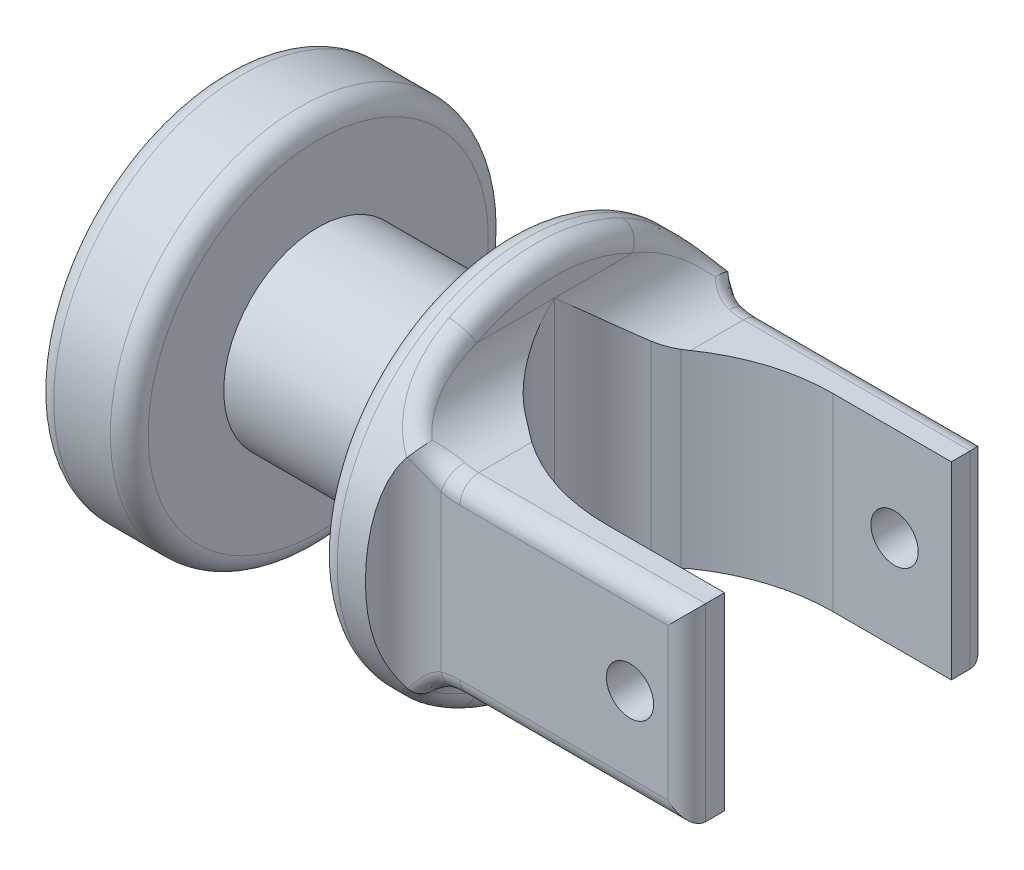
SolidWorks part; units mm, degrees
ref_plane "Front Plane" through (0, 0, 0) normal (0, 0, 1) x (1, 0, 0)
ref_plane "Top Plane" through (0, 0, 0) normal (0, 1, 0) x (1, 0, 0)
ref_plane "Right Plane" through (0, 0, 0) normal (1, 0, 0) x (0, 0, -1)
sketch "Sketch1" plane through (0, 0, 0) normal (1, 0, 0) x (0, 0, -1)
  circle A0 centre (0, 0) radius 25.4
  dimension "D1" = 50.8
extrude "Boss-Extrude1" add sketch "Sketch1" along normal blind 12.7
sketch "Sketch2" plane through (12.7, 0, 0) normal (1, 0, 0) x (0, 0, -1)
  circle A0 centre (0, 0) radius 12.7
  dimension "D1" = 25.4
extrude "Boss-Extrude2" add sketch "Sketch2" along normal blind 25.4
sketch "Sketch3" plane through (38.1, 0, 0) normal (1, 0, 0) x (0, 0, -1)
  circle A0 centre (0, 0) radius 25.4
  circle A1 centre (0, 0) radius 25.4 construction
extrude "Boss-Extrude3" add sketch "Sketch3" along normal blind 6.35
sketch "Sketch4" plane through (44.45, 0, 0) normal (1, 0, 0) x (0, 0, -1)
  line L0 (0, 25.4) -> (0, 0) construction
  line L1 (-25.4, 0) -> (25.4, 0) construction
  line L2 (-10.16, 12.7) -> (-20.32, -12.7) construction
  line L3 (10.16, -12.7) -> (20.32, -12.7)
  line L4 (10.16, -12.7) -> (10.16, 12.7)
  line L5 (10.16, 12.7) -> (20.32, 12.7)
  line L6 (20.32, -12.7) -> (20.32, 12.7)
  line L7 (10.16, -12.7) -> (20.32, 12.7) construction
  line L8 (10.16, 12.7) -> (20.32, -12.7) construction
  line L9 (-10.16, -12.7) -> (-20.32, 12.7) construction
  line L10 (-20.32, -12.7) -> (-20.32, 12.7)
  line L11 (-10.16, 12.7) -> (-20.32, 12.7)
  line L12 (-10.16, -12.7) -> (-10.16, 12.7)
  line L13 (-10.16, -12.7) -> (-20.32, -12.7)
  circle A0 centre (0, 0) radius 25.4 construction
  point P5 (15.24, 0)
  point P17 (-15.24, 0)
  dimension "D1" = 10.16
  dimension "D2" = 10.16
  dimension "D3" = 25.4
extrude "Boss-Extrude4" add sketch "Sketch4" along normal blind 38.1
fillet "Fillet1" radius 7.62 4 edges at (44.45, 12.7, 15.24) (44.45, 12.7, -15.24) (44.45, -12.7, -15.24) (44.45, -12.7, 15.24)
fillet "Fillet2" radius 5.08 2 edges at (44.45, 0, -20.32) (44.45, 0, 20.32)
fillet "Fillet3" radius 10.16 2 edges at (44.45, 0, -10.16) (44.45, 0, 10.16)
fillet "Fillet4" radius 2.54 20 edges at (47.9198, 13.9294, -20.582) (50.7814, 12.8097, -20.32) (48.6697, 13.5007, 20.3934) (50.7814, 12.8097, 20.32) (48.6697, -13.5007, -20.3934) (50.7814, -12.8097, -20.32) (47.9198, -13.9294, 20.582) (50.7814, -12.8097, 20.32) (44.8773, 17.8041, -18.1156) (44.8773, 17.8041, 18.1156) (44.8773, -17.8041, 18.1156) (44.8773, -17.8041, -18.1156) (82.55, 0, 20.32) (82.55, 0, -20.32) (67.31, 12.7, -20.32) (67.31, 12.7, 20.32) (67.31, -12.7, -20.32) (67.31, -12.7, 20.32) (44.45, 25.4, 0) (44.45, -25.4, 0)
fillet "Fillet5" radius 2.54 3 edges at (0, 0, -25.4) (12.7, 0, -25.4) (38.1, 0, -25.4)
sketch "Sketch5" plane through (0, -12.7, 0) normal (0, -1, 0) x (1, 0, 0)
  line L0 (0, 0) -> (69.85, 0) construction
  line L1 (0, 22.86) -> (0, -22.86) construction
  line L2 (82.55, 17.78) -> (82.55, 10.16) construction
  line L3 (57.15, -15.24) -> (82.55, -15.24)
  line L4 (57.15, -15.24) -> (57.15, 15.24)
  line L5 (57.15, 15.24) -> (82.55, 15.24)
  line L6 (82.55, -15.24) -> (82.55, 15.24)
  line L7 (57.15, -15.24) -> (82.55, 15.24) construction
  line L8 (57.15, 15.24) -> (82.55, -15.24) construction
  dimension "D1" = 30.48
  dimension "D2" = 25.4
extrude "Cut-Extrude1" cut sketch "Sketch5" against normal through all
fillet "Fillet6" radius 50.8 2 edges at (57.15, 0, -10.16) (57.15, 0, 10.16)
fillet "Fillet7" radius 25.4 2 edges at (57.15, 0, -15.24) (57.15, 0, 15.24)
sketch "Sketch6" plane through (0, 0, 15.24) normal (0, 0, -1) x (-1, 0, 0)
  line L0 (-82.55, 12.7) -> (-82.55, -12.7) construction
  circle A0 centre (-74.93, 0) radius 3.175
  point P2 (-82.55, 0)
  dimension "D2" = 6.35
  dimension "D1" = 7.62
extrude "Cut-Extrude2" cut sketch "Sketch6" against normal through all both and the other way through all
